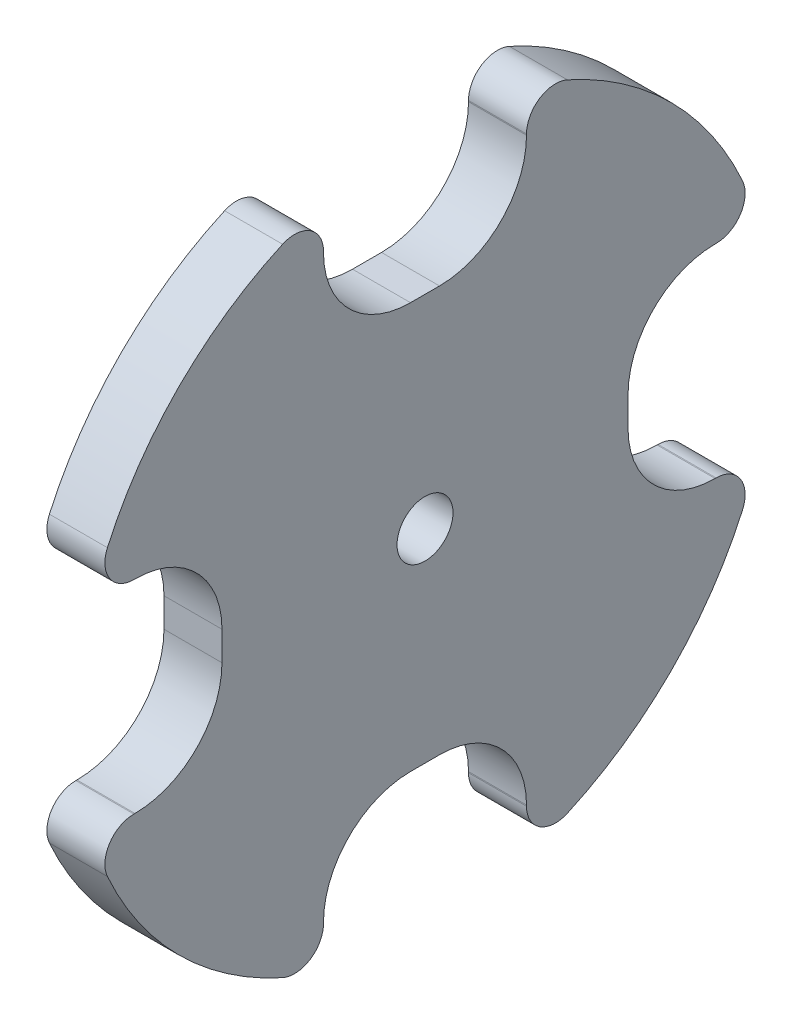
SolidWorks part; units mm, degrees
ref_plane "Front Plane" through (0, 0, 0) normal (0, 0, 1) x (1, 0, 0)
ref_plane "Top Plane" through (0, 0, 0) normal (0, 1, 0) x (1, 0, 0)
ref_plane "Right Plane" through (0, 0, 0) normal (1, 0, 0) x (0, 0, -1)
sketch "Sketch1" plane through (0, 0, 0) normal (1, 0, 0) x (0, 0, -1)
  line L0 (-3.5, 10) -> (-3.5, 11.4782)
  line L1 (-0.5, 7) -> (0.5, 7)
  line L2 (3.5, 10) -> (3.5, 11.4782)
  line L3 (0, -3.2079) -> (0, 17.8731) construction
  line L4 (-13.8591, 0) -> (8.5051, 0) construction
  circle A0 centre (0, 0) radius 12
  arc A1 (0.5, 7) -> (3.5, 10) centre (0.5, 10) ccw
  arc A2 (-0.5, 7) -> (-3.5, 10) centre (-0.5, 10) cw
  circle A3 centre (0, 0) radius 0.965
  point P8 (0, 12)
  point P18 (0, -1.81)
  point P19 (0, 1.81)
  dimension "D1" = 24
  dimension "D4" = 3
  dimension "D5" = 3
  dimension "D7" = 1.93
  dimension "D2" = 5
  dimension "D3" = 7
extrude "Boss-Extrude1" add sketch "Sketch1" along normal blind 2 contours L1 A2 L0 A0 L2 A1 A3 | A2 L1 A1 L2 A0 L0 region at (0, 7.6413, 2.8587) region at (0, 9.6417, 0)
extrude "Cut-Extrude1" cut sketch "Sketch1<3>" along normal through all contours A2 L1 A1 L2 A0 L0 region at (0, 9.6417, 0)
sketch "Sketch1<3>" plane through (0, 0, 0) normal (1, 0, 0) x (0, 0, -1) same geometry as "Sketch1"
pattern_circular "CirPattern3" count 4 over 360 about axis through (2, 0, 0) along (-1, 0, 0) of "Cut-Extrude1"
fillet "Fillet5" radius 1 8 edges at (1, -11.4782, -3.5) (1, -11.4782, 3.5) (1, -3.5, 11.4782) (1, 3.5, 11.4782) (1, -3.5, -11.4782) (1, 3.5, -11.4782) (1, 11.4782, -3.5) (1, 11.4782, 3.5)
